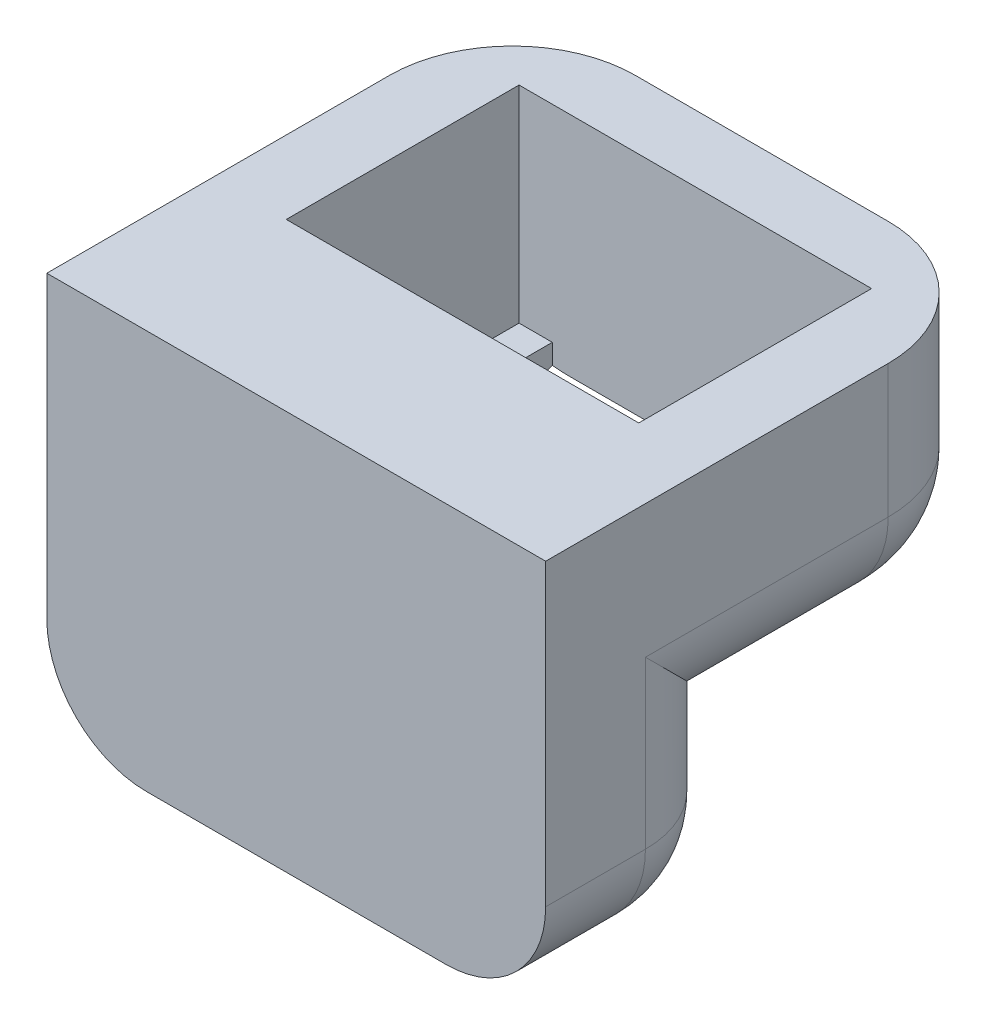
SolidWorks part; units mm, degrees
ref_plane "Front Plane" through (0, 0, 0) normal (0, 0, 1) x (1, 0, 0)
ref_plane "Top Plane" through (0, 0, 0) normal (0, 1, 0) x (1, 0, 0)
ref_plane "Right Plane" through (0, 0, 0) normal (1, 0, 0) x (0, 0, -1)
sketch "Sketch1" plane through (0, 0, 0) normal (0, 1, 0) x (1, 0, 0)
  line L1 (-7.5, 7) -> (7.5, 7)
  line L2 (-7.5, 7) -> (-7.5, -7)
  line L3 (-7.5, -7) -> (7.5, -7)
  line L4 (7.5, 7) -> (7.5, -7)
  line L5 (-7.5, 7) -> (7.5, -7) construction
  line L6 (-7.5, -7) -> (7.5, 7) construction
  point P0 (0, 0)
  dimension "D1" = 15
  dimension "D2" = 14
extrude "Boss-Extrude1" add sketch "Sketch1" along normal blind 7
fillet "Fillet1" radius 3.7 2 edges at (-7.5, 3.5, -7) (7.5, 3.5, -7)
sketch "Sketch2" plane through (0, 7, 0) normal (0, 1, 0) x (1, 0, 0)
  line L0 (3.8, 7) -> (-3.8, 7) construction
  line L1 (-5.3, 5) -> (5.3, 5)
  line L2 (-5.3, 5) -> (-5.3, -2)
  line L3 (-5.3, -2) -> (5.3, -2)
  line L4 (5.3, 5) -> (5.3, -2)
  point P6 (0, 7)
  point P7 (0, 5)
  dimension "D1" = 2
  dimension "D2" = 10.6
  dimension "D3" = 7
extrude "Cut-Extrude1" cut sketch "Sketch2" against normal blind 6.2
sketch "Sketch3" plane through (0, 0.8, 0) normal (0, 1, 0) x (1, 0, 0)
  line L0 (5.3, 5) -> (-5.3, 5) construction
  line L1 (-4.3, 5) -> (4.3, 5)
  line L2 (-4.3, 5) -> (-4.3, -1)
  line L3 (-4.3, -1) -> (4.3, -1)
  line L4 (4.3, 5) -> (4.3, -1)
  line L5 (-5.3, 5) -> (-5.3, -2) construction
  line L6 (5.3, -2) -> (5.3, 5) construction
  line L7 (-5.3, -2) -> (5.3, -2) construction
  dimension "D1" = 1
  dimension "D2" = 1
  dimension "D3" = 1
extrude "Cut-Extrude2" cut sketch "Sketch3" against normal through all
sketch "Sketch4" plane through (0, 0, 0) normal (0, -1, 0) x (1, 0, 0)
  line L1 (-7.5, 1) -> (7.5, 1)
  line L2 (-7.5, 1) -> (-7.5, 7)
  line L3 (-7.5, 7) -> (7.5, 7)
  line L4 (7.5, 1) -> (7.5, 7)
  line L5 (-7.5, -3.3) -> (-7.5, 7) construction
  line L6 (7.5, 7) -> (7.5, -3.3) construction
extrude "Boss-Extrude2" add sketch "Sketch4" along normal blind 5
fillet "Fillet8" radius 3 2 edges at (-7.5, -5, 4) (7.5, -5, 4)
fillet "Fillet9" radius 3 4 edges at (-6.4163, 0, -5.9163) (6.4163, 0, -5.9163) (-7.5, 0, -1.15) (7.5, 0, -1.15)
fillet "Fillet10" radius 3 5 edges at (-7.5, 0.5, 1) (-6.6213, -4.1213, 1) (7.5, 0.5, 1) (6.6213, -4.1213, 1) (0, -5, 1)
